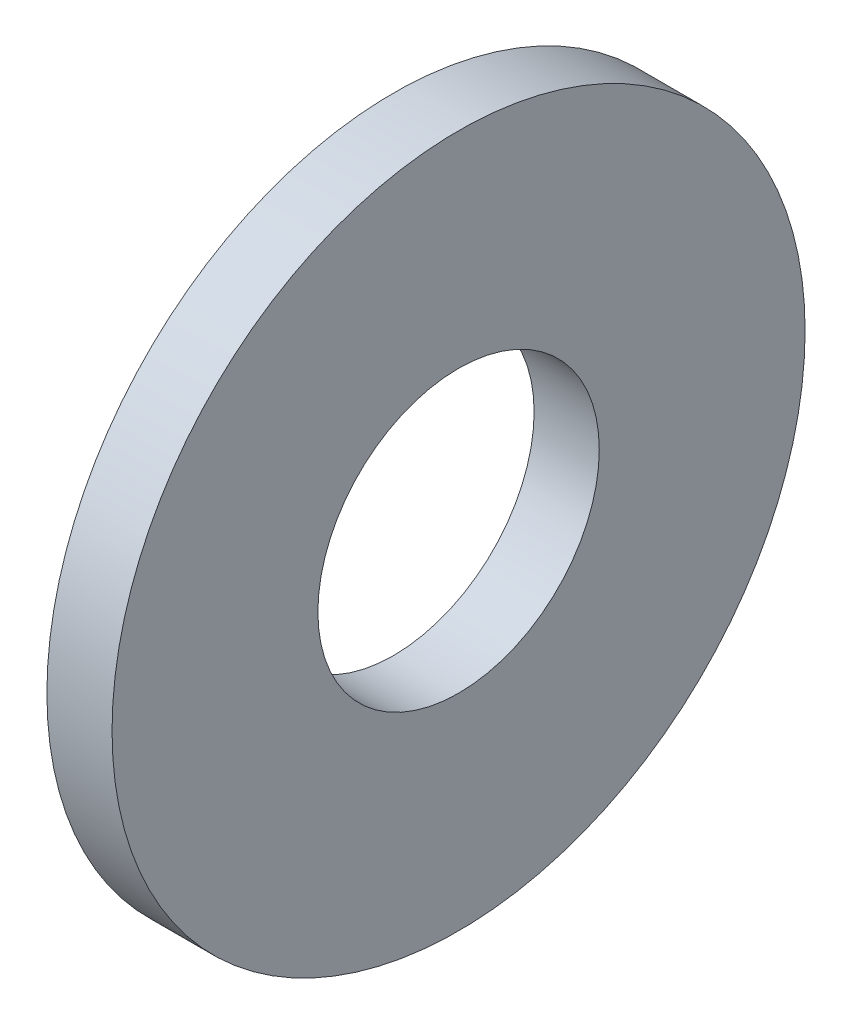
SolidWorks part; units mm, degrees
ref_plane "Front Plane" through (0, 0, 0) normal (0, 0, 1) x (1, 0, 0)
ref_plane "Top Plane" through (0, 0, 0) normal (0, 1, 0) x (1, 0, 0)
ref_plane "Right Plane" through (0, 0, 0) normal (1, 0, 0) x (0, 0, -1)
sketch "Sketch1" plane through (0, 0, 0) normal (1, 0, 0) x (0, 0, -1)
  circle A0 centre (0, 0) radius 6.35
  circle A1 centre (0, 0) radius 2.5781
  dimension "OD" = 12.7
  dimension "ID" = 5.1562
extrude "Boss-Extrude1" add sketch "Sketch1" along normal blind 1.1938
ref_axis "Center Axis 1" through (8.8544, 0, 0) along (-1, 0, 0)
ref_plane "Contact Plane 1" through (0, 0, 0) normal (-1, 0, 0) x (0, 0, 1)
